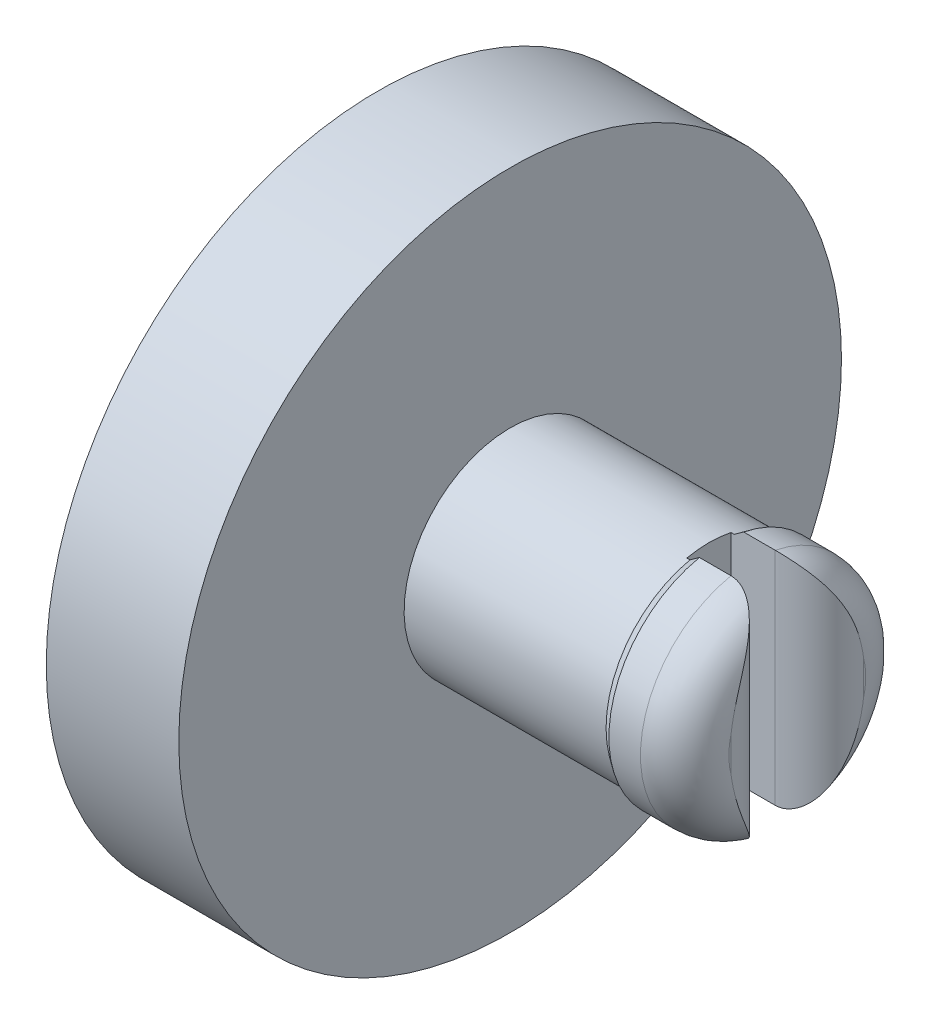
SolidWorks part; units mm, degrees
ref_plane "Front Plane" through (0, 0, 0) normal (1, 0, 0) x (0, 1, 0)
ref_plane "Top Plane" through (0, 0, 0) normal (0, 0, 1) x (0, 1, 0)
ref_plane "Right Plane" through (0, 0, 0) normal (0, 1, 0) x (-1, 0, 0)
sketch "Sketch1" plane through (0, 0, 0) normal (1, 0, 0) x (0, 1, 0)
  circle A0 centre (0, 0) radius 7.5
  dimension "D1" = 15
extrude "Boss-Extrude1" add sketch "Sketch1" along normal blind 3
sketch "Sketch2" plane through (3, 0, 0) normal (1, 0, 0) x (0, 0, -1)
  circle A0 centre (0, 0) radius 2.4
  dimension "D1" = 4.8
extrude "Boss-Extrude2" add sketch "Sketch2" along normal blind 4.5
sketch "Sketch3" plane through (7.5, 0, 0) normal (1, 0, 0) x (0, 1, 0)
  line L0 (-2.5005, 0.5) -> (2.5005, 0.5)
  line L1 (2.5005, -0.5) -> (-2.5005, -0.5)
  arc A0 (-2.5005, -0.5) -> (2.5005, -0.5) centre (0, 0) ccw
  arc A1 (2.5005, 0.5) -> (-2.5005, 0.5) centre (0, 0) ccw
  dimension "D1" = 5.1
  dimension "D2" = 1
extrude "Boss-Extrude3" add sketch "Sketch3" along normal blind 2
fillet "Fillet1" radius 1 2 edges at (9.5, 0, 0.5) (9.5, 0, 2.55)
fillet "Fillet2" radius 1 2 edges at (9.5, 0, -0.5) (9.5, 0, -2.55)
chamfer "Chamfer2" distance 0.2 angle 55 2 edges at (7.5, 0, -2.55) (7.5, 0, 2.55) first distance on face at (7.5, 0, -1.4875) first distance on face at (7.5, 0, 1.4875)
